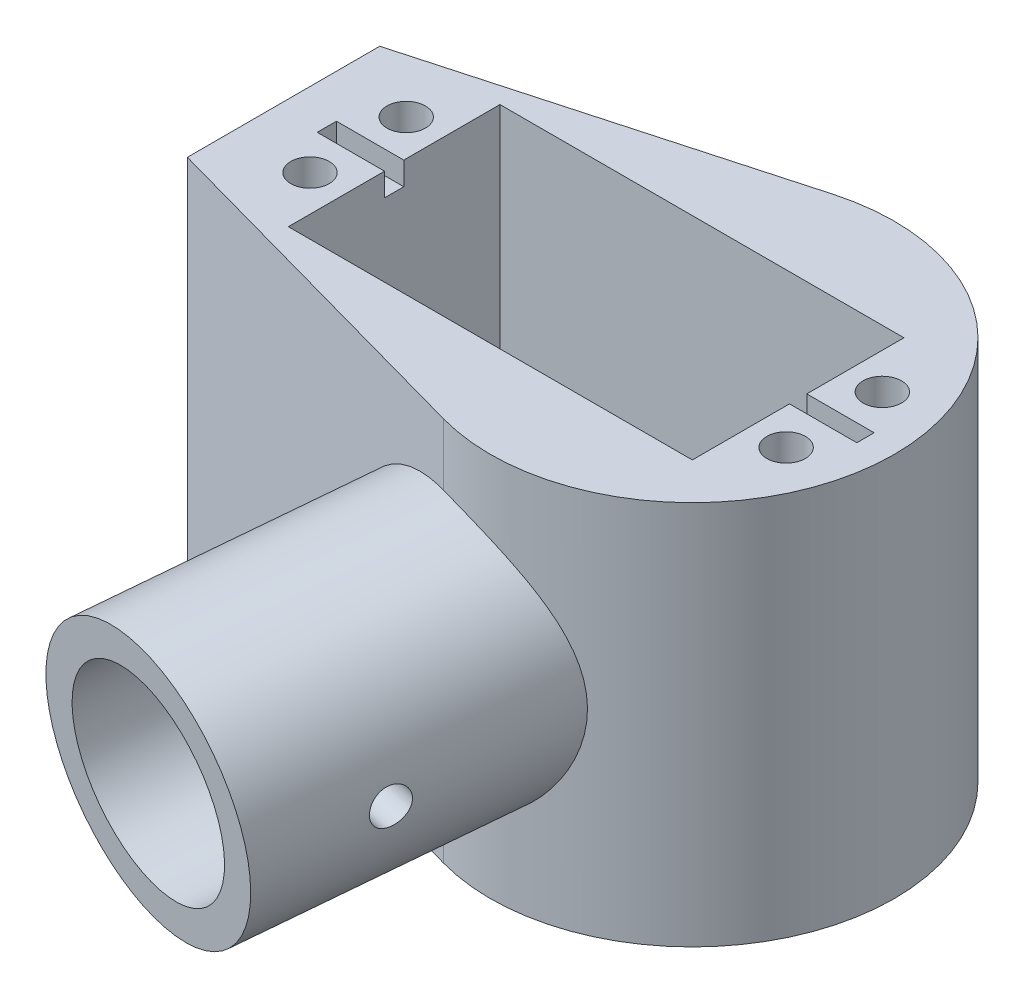
SolidWorks part; units mm, degrees
ref_plane "Front" through (0, 0, 0) normal (0, 0, 1) x (1, 0, 0)
ref_plane "Top" through (0, 0, 0) normal (0, 1, 0) x (1, 0, 0)
ref_plane "Right" through (0, 0, 0) normal (1, 0, 0) x (0, 0, -1)
sketch "Sketch1" plane through (0, 0, 0) normal (0, 1, 0) x (1, 0, 0)
  line L0 (-10.25, 0) -> (17, 0) construction
  line L1 (-37.5, -10) -> (17, -10)
  line L2 (-37.5, -10) -> (-37.5, 10)
  line L3 (-37.5, 10) -> (17, 10)
  line L4 (17, -10) -> (17, 10)
  line L5 (-37.5, -10) -> (17, 10) construction
  line L6 (-37.5, 10) -> (17, -10) construction
  line L7 (-42.5, -10) -> (-42.5, 10)
  line L8 (-30.25, -10) -> (9.75, -10)
  line L9 (-30.25, -10) -> (-30.25, 10)
  line L10 (-30.25, 10) -> (9.75, 10)
  line L11 (9.75, -10) -> (9.75, 10)
  line L12 (-30.25, -10) -> (9.75, 10) construction
  line L13 (-30.25, 10) -> (9.75, -10) construction
  line L14 (-42.5, 10) -> (-5.6152, 20.2354)
  line L15 (-42.5, -10) -> (-5.6152, -20.2354)
  line L16 (-42.5, 0) -> (-39.8632, 0) construction
  circle A0 centre (0, 0) radius 21
  circle A1 centre (0, 0) radius 6
  point P3 (-10.25, 0)
  dimension "D1" = 42
  dimension "D4" = 12
  dimension "D2" = 20
  dimension "D3" = 54.5
  dimension "D5" = 37.5
  dimension "D6" = 20
  dimension "D7" = 40
  dimension "D8" = 5
  dimension "D9" = 10
extrude "Boss-Extrude1" add sketch "Sketch1" along normal blind 40 contours A0 L14 L7 L15 L1 L2 L3 | L1 L9 L3 L2 | L10 A0 L8 L11 A1 | A0 L3 L9 L1 | A0 L10 L3 L4 L1 L8 | L11 L1 L4 L3 region at (-33.875, 0, 0) region at (-33.875, 0, 10.5476) region at (-25.1857, 0, 0) region at (-6.4396, 0, 0) region at (-4.3581, 0, 10.5763) region at (13.375, 0, 0)
sketch "Sketch2" plane through (0, 40, 0) normal (0, 1, 0) x (1, 0, 0)
  line L1 (-31, -11) -> (11, -11)
  line L2 (-31, -11) -> (-31, 11)
  line L3 (-31, 11) -> (11, 11)
  line L4 (11, -11) -> (11, 11)
  line L5 (-31, -11) -> (11, 11) construction
  line L6 (-31, 11) -> (11, -11) construction
  point P0 (-10, 0)
  dimension "D1" = 22
  dimension "D2" = 42
  dimension "D3" = 10
extrude "Cut-Extrude1" cut sketch "Sketch2" against normal blind 25
sketch "Sketch3" plane through (0, 40, 0) normal (0, 1, 0) x (1, 0, 0)
  circle A0 centre (14.75, 5) radius 2
  circle A1 centre (14.75, -5) radius 2
  circle A2 centre (-34.75, 5) radius 2
  circle A3 centre (-34.75, -5) radius 2
  dimension "D1" = 10
  dimension "D3" = 4
  dimension "D4" = 4
  dimension "D2" = 5
  dimension "D6" = 34.75
  dimension "D5" = 2
extrude "Cut-Extrude2" cut sketch "Sketch3" against normal blind 12
sketch "Sketch4" plane through (0, 15, 0) normal (0, 1, 0) x (1, 0, 0)
  circle A0 centre (0, 0) radius 9.5
  dimension "D1" = 19
extrude "Cut-Extrude3" cut sketch "Sketch4" against normal blind 5
sketch "Sketch5" plane through (0, 0, 0) normal (0, -1, 0) x (1, 0, 0)
  circle A0 centre (0, 0) radius 9.5
  dimension "D1" = 19
extrude "Cut-Extrude4" cut sketch "Sketch5" against normal blind 6
sketch "Sketch7" plane through (0, 40, 0) normal (0, 1, 0) x (1, 0, 0)
  line L0 (-31, 11) -> (-31, -11) construction
  line L1 (-38, -1) -> (-24, -1)
  line L2 (-38, -1) -> (-38, 1)
  line L3 (-38, 1) -> (-24, 1)
  line L4 (-24, -1) -> (-24, 1)
  line L5 (-38, -1) -> (-24, 1) construction
  line L6 (-38, 1) -> (-24, -1) construction
  line L7 (11, -11) -> (11, 11) construction
  line L8 (4, -0.9) -> (18, -0.9)
  line L9 (4, -0.9) -> (4, 0.9)
  line L10 (4, 0.9) -> (18, 0.9)
  line L11 (18, -0.9) -> (18, 0.9)
  line L12 (4, -0.9) -> (18, 0.9) construction
  line L13 (4, 0.9) -> (18, -0.9) construction
  line L14 (-31, 11) -> (-31, -11) construction
  line L15 (11, -11) -> (11, 11) construction
  line L16 (-31, 11) -> (-31, -11)
  line L17 (11, -11) -> (11, 11)
  point P0 (-31, 0)
  point P7 (11, 0)
  line M9 (11, 11) -> (11, -11)
  line M11 (-31, -11) -> (-31, 11)
  dimension "D1" = 2
  dimension "D2" = 14
  dimension "D3" = 14
  dimension "D4" = 1.8
extrude "Cut-Extrude5" cut sketch "Sketch7" against normal blind 2.4 contours L3 L2 L1 M11 | L8 L11 L10 M9 region at (-34.5, 40, 0) region at (14.5, 40, 0)
ref_plane "Plane5" through (0, 34, 0) normal (0, 1, 0) x (1, 0, 0)
sketch "Sketch8" plane through (0, 34, 0) normal (0, 1, 0) x (1, 0, 0)
  line L0 (-34.75, 8.5) -> (-31, 8.5)
  line L1 (-34.75, 8.5) -> (-36.7707, 8.5)
  line L2 (-36.7707, 8.5) -> (-38.7915, 5)
  line L3 (-38.7915, 5) -> (-36.7707, 1.5)
  line L4 (-36.7707, 1.5) -> (-34.75, 1.5)
  line L7 (-31, 11) -> (-31, 1) construction
  line L8 (-34.75, 1.5) -> (-31, 1.5)
  line L9 (-31, 1.5) -> (-31, 8.5)
  line L10 (-34.75, -1.5) -> (-36.7707, -1.5)
  line L11 (-31.7189, 3.25) -> (-30.8529, 4.75)
  line L12 (-31.7189, 6.75) -> (-32.5849, 8.25)
  line L13 (-36.7707, -1.5) -> (-38.7915, -5)
  line L14 (-38.7915, -5) -> (-36.7707, -8.5)
  line L15 (-36.7707, -8.5) -> (-34.75, -8.5)
  line L16 (-34.75, -8.5) -> (-31, -8.5)
  line L17 (-31, -8.5) -> (-31, -1.5)
  line L18 (-34.75, -1.5) -> (-31, -1.5)
  line L19 (-10, 11) -> (-10, 7.9919) construction
  line L20 (11, 11) -> (-31, 11) construction
  line L21 (14.75, -1.5) -> (11, -1.5)
  line L22 (11, -8.5) -> (11, -1.5)
  line L23 (14.75, -8.5) -> (11, -8.5)
  line L24 (16.7707, -8.5) -> (14.75, -8.5)
  line L25 (18.7915, -5) -> (16.7707, -8.5)
  line L26 (16.7707, -1.5) -> (18.7915, -5)
  line L27 (14.75, -1.5) -> (16.7707, -1.5)
  line L28 (11, 1.5) -> (11, 8.5)
  line L29 (14.75, 1.5) -> (11, 1.5)
  line L30 (16.7707, 1.5) -> (14.75, 1.5)
  line L31 (18.7915, 5) -> (16.7707, 1.5)
  line L32 (16.7707, 8.5) -> (18.7915, 5)
  line L33 (14.75, 8.5) -> (16.7707, 8.5)
  line L34 (14.75, 8.5) -> (11, 8.5)
  line L35 (-31, 11) -> (-31, -11) construction
  circle A0 centre (-34.75, 5) radius 3.5 construction
  circle A1 centre (14.75, 5) radius 3.5 construction
  dimension "D1" = 7
  dimension "D2" = 2
  dimension "D3" = 10
extrude "Cut-Extrude6" [suppressed] cut sketch "Sketch8" against normal blind 3.5 contours L18 L10 L13 L14 L15 L16 L17 | L8 L9 L0 L1 L2 L3 L4 | L33 L34 L28 L29 L30 L31 L32 | L27 L21 L22 L23 L24 L25 L26
ref_plane "Plane6" through (0, 20, 0) normal (0, 1, 0) x (1, 0, 0)
ref_axis "Axis1" through (80.9, 20, 0) along (-1, 0, 0)
ref_plane "Plane7" through (0, 0.2185, -2.0791) normal (0, 0.1045, -0.9945) x (-1, 0, 0)
ref_axis "Axis2" through (0, -50, -7.3573) along (0, 0.9945, 0.1045)
ref_plane "Plane8" through (0.4084, 0.2098, -1.9965) normal (0.1994, 0.1024, -0.9746) x (0, 0.9945, 0.1045)
ref_plane "Plane9" through (-8.9619, -4.6044, 43.8077) normal (0.1994, 0.1024, -0.9746) x (0, 0.9945, 0.1045)
sketch "Sketch9" plane through (-8.9619, -4.6044, 43.8077) normal (0.1994, 0.1024, -0.9746) x (0, 0.9945, 0.1045)
  line L0 (41.896, -2.3239) -> (2.1152, -1.4903) construction
  circle A0 centre (22.0056, -1.9071) radius 10.05
  circle A1 centre (22.0056, -1.9071) radius 13.5
  dimension "D1" = 20.1
  dimension "D2" = 27
extrude "Boss-Extrude2" add sketch "Sketch9" along normal up to next
ref_plane "Plane10" through (-3.9777, -2.0436, 19.4438) normal (-0.1994, -0.1024, 0.9746) x (0.9799, -0.0208, 0.1983)
sketch "Sketch10" plane through (-3.9777, -2.0436, 19.4438) normal (-0.1994, -0.1024, 0.9746) x (0.9799, -0.0208, 0.1983)
  circle A0 centre (-1.9071, 22.0056) radius 10.05 construction
  circle A1 centre (-1.9071, 22.0056) radius 10.05
extrude "Boss-Extrude3" add sketch "Sketch10" against normal up to next
ref_axis "Axis3" through (-5.9743, 19.8155, 21.9905) along (-0.1994, -0.1024, 0.9746)
ref_plane "Plane11" through (0, 21.8851, 2.3002) normal (0, 0.9945, 0.1045) x (-0.1994, -0.1024, 0.9746)
ref_plane "Plane12" through (-1.8688, 0.0397, -0.3781) normal (-0.9799, 0.0208, -0.1983) x (-0.1994, -0.1024, 0.9746)
sketch "Sketch11" plane through (-1.8688, 0.0397, -0.3781) normal (-0.9799, 0.0208, -0.1983) x (-0.1994, -0.1024, 0.9746)
  line L0 (44.9514, 22.0056) -> (32.4514, 22.0056) construction
  line L1 (44.9514, 8.5056) -> (44.9514, 35.5056) construction
  circle A0 centre (32.4514, 22.0056) radius 1.9
  dimension "D2" = 3.8
  dimension "D1" = 12.5
extrude "Cut-Extrude7" cut sketch "Sketch11" against normal mid plane 27
